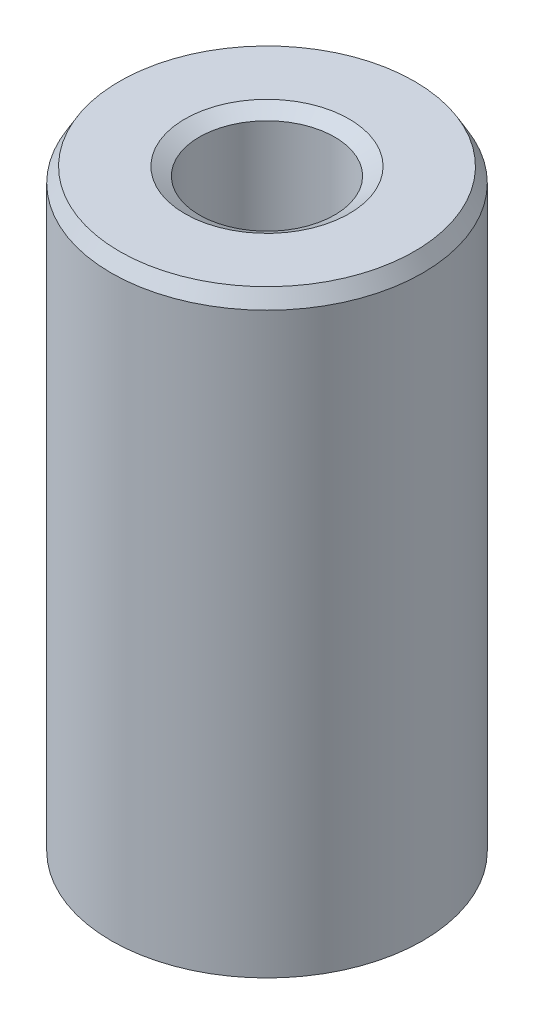
SolidWorks part; units mm, degrees
ref_plane "Front Plane" through (0, 0, 0) normal (0, 0, 1) x (1, 0, 0)
ref_plane "Top Plane" through (0, 0, 0) normal (0, 1, 0) x (1, 0, 0)
ref_plane "Right Plane" through (0, 0, 0) normal (1, 0, 0) x (0, 0, -1)
sketch "Sketch1" plane through (0, 0, 0) normal (0, 1, 0) x (1, 0, 0)
  circle A0 centre (0, 0) radius 17.5
  dimension "SLEEVE_OD" = 35
extrude "Boss-Extrude1" add sketch "Sketch1" along normal blind 67.5279
sketch "Sketch2" plane through (0, 0, 0) normal (0, 1, 0) x (1, 0, 0)
  circle A0 centre (0, 0) radius 7.5976
  dimension "BORE_D" = 15.1952
extrude "Cut-Extrude1" cut sketch "Sketch2" along normal through all
chamfer "Chamfer1" distance 1.6272 angle 30 4 edges at (0, 67.5279, 7.5976) (0, 0, 7.5976) (0, 0, 17.5) (0, 67.5279, 17.5) first distance on face at (0, 67.5279, 7.5976) first distance on face at (0, 0, 7.5976) first distance on face at (0, 67.5279, 17.5)
